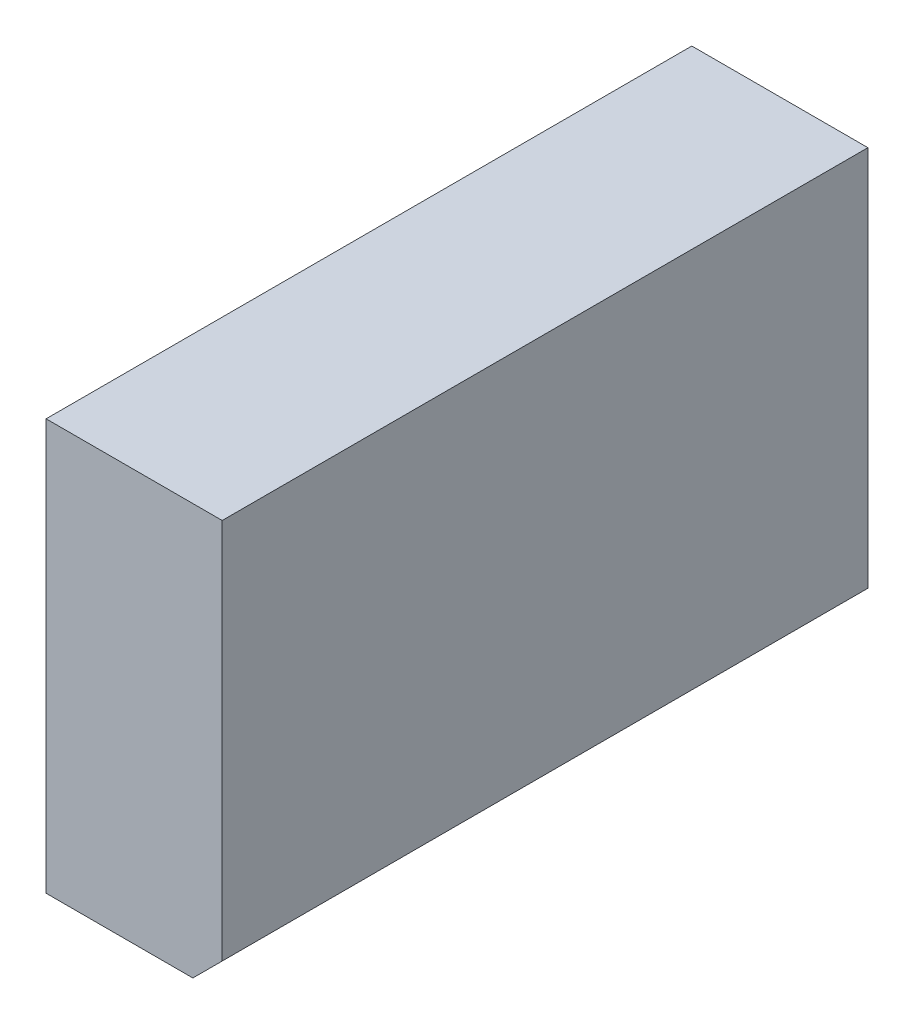
SolidWorks part; units mm, degrees
ref_plane "Front Plane" through (0, 0, 0) normal (0, 0, 1) x (1, 0, 0)
ref_plane "Top Plane" through (0, 0, 0) normal (0, 1, 0) x (1, 0, 0)
ref_plane "Right Plane" through (0, 0, 0) normal (1, 0, 0) x (0, 0, -1)
sketch "Sketch1" plane through (0, 0, 0) normal (0, 0, 1) x (1, 0, 0)
  line L1 (0, 0) -> (38.1, 0)
  line L2 (0, 0) -> (0, 88.9)
  line L3 (0, 88.9) -> (38.1, 88.9)
  line L4 (38.1, 0) -> (38.1, 88.9)
  dimension "D1" = 88.9
  dimension "D2" = 38.1
extrude "Boss-Extrude1" add sketch "Sketch1" along normal blind 139.7
chamfer "Chamfer1" distance 6.35 angle 45 1 edges at (38.1, 0, 69.85)
